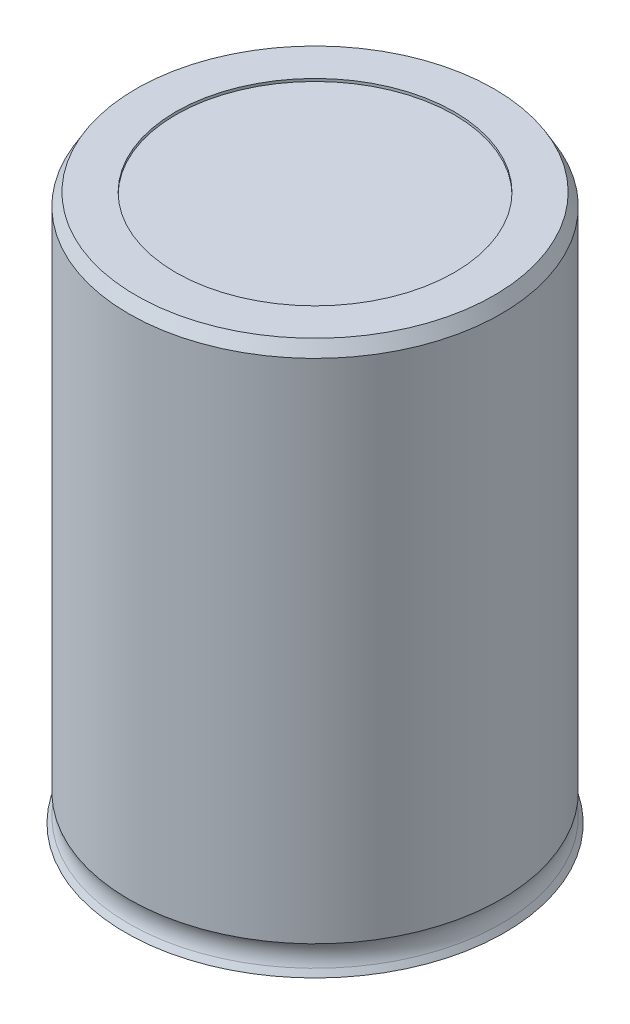
SolidWorks part; units mm, degrees
ref_plane "Front Plane" through (0, 0, 0) normal (0, 0, 1) x (1, 0, 0)
ref_plane "Top Plane" through (0, 0, 0) normal (0, 1, 0) x (1, 0, 0)
ref_plane "Right Plane" through (0, 0, 0) normal (1, 0, 0) x (0, 0, -1)
sketch "Sketch1" plane through (0, 0, 0) normal (1, 0, 0) x (0, 0, -1)
  line L0 (0, 46.5858) -> (0, -48.5118) construction
  line L1 (-17.575, 23.9559) -> (-17.575, -23.9121)
  line L2 (-17.575, 23.9559) -> (-16.9, 25.125)
  line L3 (-16.9, 25.125) -> (-13.15, 25.125)
  line L4 (-17.575, -25.9121) -> (-17.9, -26.475)
  line L5 (-17.9, -26.475) -> (-12.4, -26.475)
  line L6 (-12.4, -26.475) -> (-12.4, -24.875)
  line L7 (-12.4, -24.875) -> (0, -24.875)
  line L8 (-13.15, 25.125) -> (-13.15, 24.875)
  line L9 (-13.15, 24.875) -> (0, 24.875)
  line L10 (-13.15, 25.125) -> (0, 25.125) construction
  line L11 (0, -24.875) -> (0, 24.875)
  arc A0 (-17.575, -23.9121) -> (-17.575, -25.9121) centre (-19.6703, -24.9121) cw
  point P16 (0, 0)
  dimension "D3" = 35.8
  dimension "D1" = 35.15
  dimension "D2" = 30
  dimension "D4" = 51.6
  dimension "D5" = 33.8
  dimension "D6" = 24.8
  dimension "D7" = 1.6
  dimension "D8" = 26.3
  dimension "D9" = 0.25
  dimension "D10" = 2
revolve "Revolve1" add sketch "Sketch1" angle 360 about L11
sketch "Sketch3" plane through (0, 0, 0) normal (0, 1, 0) x (1, 0, 0)
  line L0 (-9.2485, 0) -> (10.3696, 0) construction
  line L1 (0, 8.0341) -> (0, -6.4927) construction
  line L2 (4.205, 0) -> (4.205, -2.896) construction
  line L3 (-4.205, 0) -> (-4.205, 3.4098) construction
  circle A0 centre (4.905, 0) radius 0.7
  circle A1 centre (-4.905, 0) radius 0.7
  dimension "D1" = 8.41
  dimension "D2" = 1.4
extrude "Boss-Extrude1" add sketch "Sketch3" against normal blind 7 from surface starting at face at (0, -24.875, -12.4)
